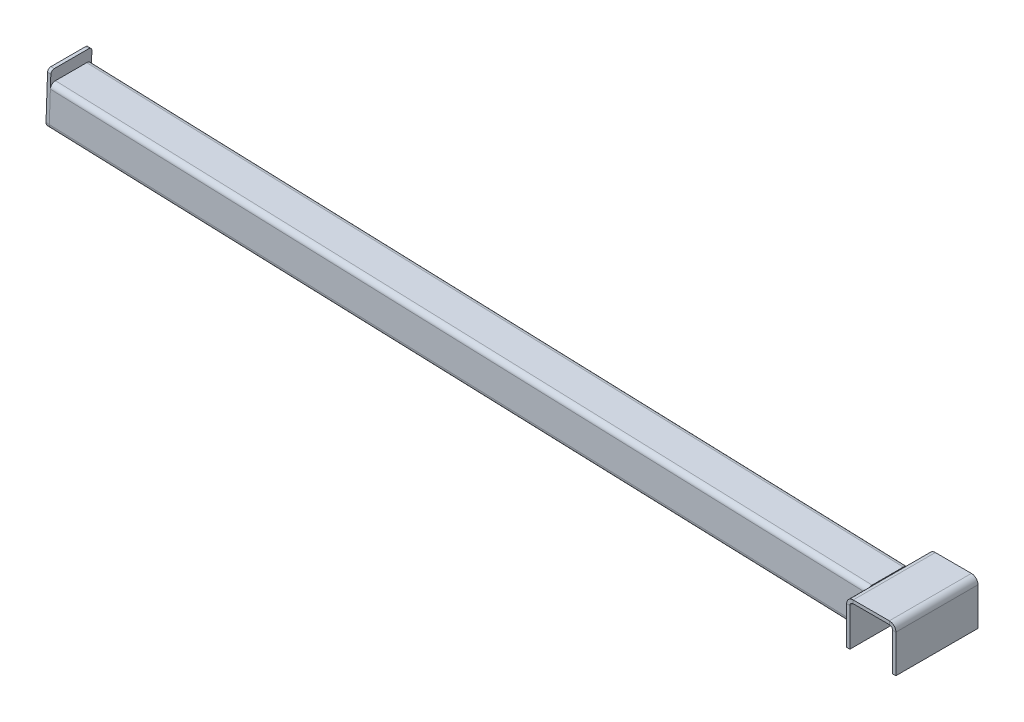
SolidWorks part; units mm, degrees
note: The reader was unsure of these and kept them because the rebuilt part matched: flange length of "Edge-Flange1".
ref_plane "Спереди" through (0, 0, 0) normal (0, 0, 1) x (1, 0, 0)
ref_plane "Сверху" through (0, 0, 0) normal (0, 1, 0) x (1, 0, 0)
ref_plane "Справа" through (0, 0, 0) normal (1, 0, 0) x (0, 0, -1)
sketch "Эскиз1" plane through (0, 0, 0) normal (0, 1, 0) x (1, 0, 0)
  line L1 (-13, -25) -> (13, -25)
  line L2 (-13, -25) -> (-13, 25)
  line L3 (-13, 25) -> (13, 25)
  line L4 (13, -25) -> (13, 25)
  line L5 (0, 25) -> (0, -25) construction
  line L6 (-13, 0) -> (13, 0) construction
  point P0 (0, 0)
  dimension "D1" = 26
  dimension "D2" = 50
base flange "Базовая кромка1" sketch "Эскиз1" thickness 2 reverse thickness direction no parameters "D1"=2
edge flange "Edge-Flange1" sketch "Эскиз11" flange profiles "Эскиз11", "Эскиз12" flange angle 90 flange length 25 flange position material outside bend radius 2 thickness 2 relief rectangular parameters "D6"=10, "D8"=1
sketch "Эскиз11" plane through (13, -2, 0) normal (-1, 0, 0) x (0, 0, -1)
  line L2 (-25, 0) -> (-25, 25)
  line L3 (-25, 25) -> (25, 25)
  line L4 (25, 25) -> (25, 0)
  line L5 (25, 0) -> (-25, 0) construction
  line L6 (25, 0) -> (-25, 0)
sketch "Эскиз12" plane through (-13, -2, 0) normal (1, 0, 0) x (0, 0, 1)
  line L0 (25, 0) -> (-25, 0) construction
  line L1 (25, 0) -> (-25, 0)
  line L2 (25, 0) -> (25, 25)
  line L3 (25, 25) -> (-25, 25)
  line L4 (-25, 25) -> (-25, 0)
bend "EdgeBend1" bend radius 2 bend angle 90 parameters "D5"=1
bend "EdgeBend2" bend radius 2 bend angle 90 parameters "D5"=2
sketch "Эскиз13" plane through (0, 0, 0) normal (0, 0, 1) x (1, 0, 0)
  line L0 (-13, -14.5) -> (-512.6954, 2.9497)
  line L2 (-15, -4) -> (-15, -27) construction
  line L3 (-15, -15.5) -> (-53.6476, -15.5) construction
  line L5 (-13, -4) -> (-13, -27) construction
  dimension "D1" = 2
  dimension "D2" = 500
  dimension "D3" = 12.5
other "Квадратная труба 2 X 2 X 0.25(1)" corner treatment miter
ref_plane "Плоскость1" through (-13, -14.5, 0) normal (-0.9994, 0.0349, 0) x (-0.0349, -0.9994, 0)
sketch "Sketch1" plane through (-13, -14.5, 0) normal (-0.9994, 0.0349, 0) x (-0.0349, -0.9994, 0)
  line L0 (-9.5, -11) -> (9.5, -11)
  line L1 (-11, -9.5) -> (-11, 9.5)
  line L2 (9.5, 11) -> (-9.5, 11)
  line L3 (11, 9.5) -> (11, -9.5)
  line L4 (-9.5, -12.5) -> (9.5, -12.5)
  line L5 (-12.5, -9.5) -> (-12.5, 9.5)
  line L6 (9.5, 12.5) -> (-9.5, 12.5)
  line L7 (12.5, 9.5) -> (12.5, -9.5)
  line L8 (0, 0) -> (11, 0) construction
  line L9 (0, 0) -> (0, 11) construction
  arc A0 (12.5, 9.5) -> (9.5, 12.5) centre (9.5, 9.5) ccw
  arc A1 (9.5, -12.5) -> (12.5, -9.5) centre (9.5, -9.5) ccw
  arc A2 (-12.5, -9.5) -> (-9.5, -12.5) centre (-9.5, -9.5) ccw
  arc A3 (-9.5, 12.5) -> (-12.5, 9.5) centre (-9.5, 9.5) ccw
  arc A4 (-9.5, 11) -> (-11, 9.5) centre (-9.5, 9.5) ccw
  arc A5 (11, 9.5) -> (9.5, 11) centre (9.5, 9.5) ccw
  arc A6 (9.5, -11) -> (11, -9.5) centre (9.5, -9.5) ccw
  arc A7 (-11, -9.5) -> (-9.5, -11) centre (-9.5, -9.5) ccw
  point P3 (0, 12.5)
  point P4 (12.5, 0)
  point P5 (0, -12.5)
  point P6 (-12.5, 0)
  point P7 (-12.5, 12.5)
  point P8 (-12.5, -12.5)
  point P33 (0, 0)
  point P35 (12.5, -12.5)
  point P36 (12.5, 12.5)
  point P37 (0, 0)
  dimension "D1" = 3
  dimension "Thickness" = 1.5
  dimension "V_leg" = 25
ref_plane "Плоскость2" through (-15, 0, 0) normal (-1, 0, 0) x (0, 0, 1)
sketch "Эскиз15" plane through (-15, 0, 0) normal (-1, 0, 0) x (0, 0, 1)
  line L1 (-32.3364, 0.918) -> (20.8052, 0.918)
  line L2 (-32.3364, 0.918) -> (-32.3364, -31.3615)
  line L3 (-32.3364, -31.3615) -> (20.8052, -31.3615)
  line L4 (20.8052, 0.918) -> (20.8052, -31.3615)
extrude "Вырез-Вытянуть1" cut sketch "Эскиз15" against normal through all
sketch "Эскиз16" plane through (-512.1738, 17.8855, 0) normal (-0.9994, 0.0349, 0) x (0, 0, 1)
  line L0 (-10.5, 4.5551) -> (10.5, 4.5551)
  line L1 (9.5, -2.4449) -> (-9.5, -2.4449) construction
  line L4 (12.5, -24.4449) -> (12.5, -5.4449)
  line L5 (9.5, -2.4449) -> (-9.5, -2.4449)
  line L6 (-12.5, -5.4449) -> (-12.5, -24.4449)
  line L7 (-9.5, -27.4449) -> (9.5, -27.4449)
  line L8 (12.5, -24.4449) -> (12.5, 2.5551)
  line L10 (-12.5, 2.5551) -> (-12.5, -24.4449)
  line L11 (-9.5, -27.4449) -> (9.5, -27.4449)
  arc A0 (12.5, 2.5551) -> (10.5, 4.5551) centre (10.5, 2.5551) ccw
  arc A1 (-10.5, 4.5551) -> (-12.5, 2.5551) centre (-10.5, 2.5551) ccw
  arc A4 (9.5, -27.4449) -> (12.5, -24.4449) centre (9.5, -24.4449) ccw
  arc A5 (12.5, -5.4449) -> (9.5, -2.4449) centre (9.5, -5.4449) ccw
  arc A6 (-9.5, -2.4449) -> (-12.5, -5.4449) centre (-9.5, -5.4449) ccw
  arc A7 (-12.5, -24.4449) -> (-9.5, -27.4449) centre (-9.5, -24.4449) ccw
  arc A8 (9.5, -27.4449) -> (12.5, -24.4449) centre (9.5, -24.4449) ccw
  arc A11 (-12.5, -24.4449) -> (-9.5, -27.4449) centre (-9.5, -24.4449) ccw
  dimension "D3" = 2
  dimension "D2" = 7
  dimension "D1" = 0
extrude "Бобышка-Вытянуть2" add sketch "Эскиз16" along normal blind 2 separate body
sketch "Bend-Lines1" [suppressed] plane through (0, 0, 0) normal (0, 1, 0) x (1, 0, 0)
sketch "Bounding-Box1" [suppressed] plane through (0, 0, 0) normal (0, 1, 0) x (1, 0, 0)
sheet metal parameters "Sheet-Metal4" thickness 2 parameters "D1"=2
flat pattern "Flat-Pattern4" [suppressed]
sketch "Bend-Lines2" plane through (0, 0, 0) normal (0, 1, 0) x (1, 0, 0)
sketch "Bounding-Box2" [suppressed] plane through (0, 0, 0) normal (0, 1, 0) x (1, 0, 0)
sheet metal parameters "Sheet-Metal5" thickness 2 parameters "D1"=2
flat pattern "Flat-Pattern4"
sketch "Bend-Lines2" plane through (0, 0, 0) normal (0, 1, 0) x (1, 0, 0)
  line L0 (-13.3562, 25) -> (-13.3562, -25) construction
  line L1 (13.3562, -25) -> (13.3562, 25) construction
  line L2 (-13.3562, 25) -> (-13.3562, -25) construction
  line L3 (13.3562, -25) -> (13.3562, 25) construction
sketch3d "Bounding-Box2" [suppressed]
  line L0 (38.7124, 25, 0) -> (-38.7124, 25, 0) construction
  line L1 (38.7124, -25, 0) -> (-38.7124, -25, 0) construction
  line L2 (38.7124, 25, 0) -> (38.7124, -25, 0) construction
  line L3 (-38.7124, 25, 0) -> (-38.7124, -25, 0) construction
bend of the flat pattern "Flatten-<EdgeBend1>1"
bend of the flat pattern "Flatten-<EdgeBend2>1"
